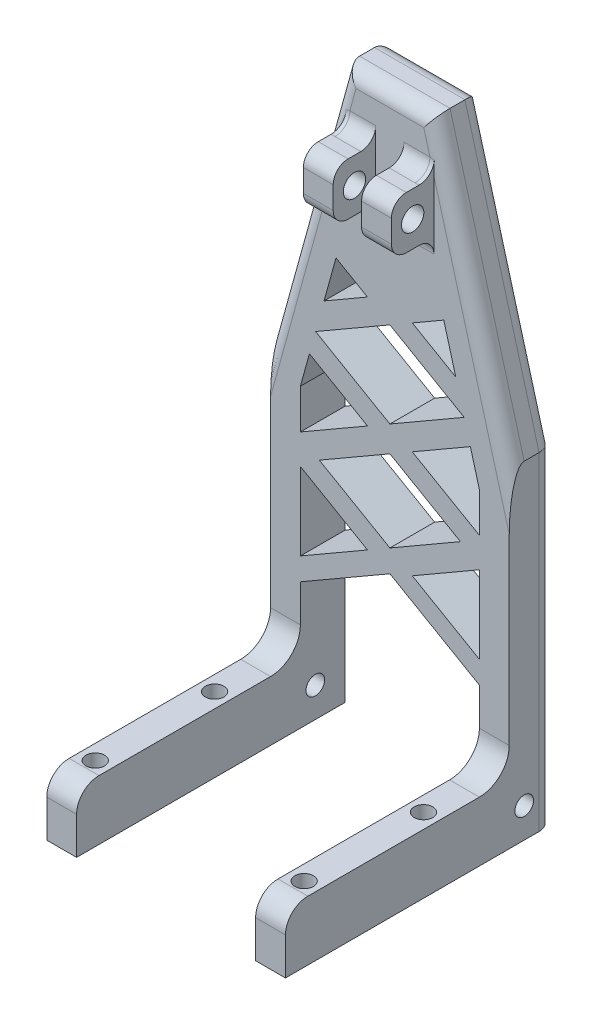
SolidWorks part; units mm, degrees
ref_plane "Front Plane" through (0, 0, 0) normal (0, 0, 1) x (1, 0, 0)
ref_plane "Top Plane" through (0, 0, 0) normal (0, 1, 0) x (1, 0, 0)
ref_plane "Right Plane" through (0, 0, 0) normal (1, 0, 0) x (0, 0, -1)
sketch "Sketch1" plane through (0, 0, 0) normal (0, 1, 0) x (1, 0, 0)
  line L0 (0, 0) -> (0, 15) construction
  line L1 (-12, -15) -> (12, -15) construction
  line L2 (-12, -15) -> (-12, 15) construction
  line L3 (-12, 15) -> (12, 15) construction
  line L4 (12, -15) -> (12, 15) construction
  line L5 (-12, -15) -> (12, 15) construction
  line L6 (-12, 15) -> (12, -15) construction
  line L7 (-12, -15) -> (-16, -15)
  line L8 (-12, -15) -> (-12, 15)
  line L9 (-12, 15) -> (-16, 15)
  line L10 (-16, -15) -> (-16, 15)
  line L11 (12, 15) -> (16, 15)
  line L12 (16, -15) -> (16, 15)
  line L13 (12, -15) -> (16, -15)
  line L14 (12, -15) -> (12, 15)
  line L15 (-14, -15) -> (-14, 15) construction
  circle A0 centre (-14, -10.5) radius 1.25
  circle A1 centre (-14, 5.5) radius 1.25
  circle A2 centre (14, -10.5) radius 1.25
  circle A3 centre (14, 5.5) radius 1.25
  point P0 (0, 0)
  dimension "D5" = 2.5
  dimension "D7" = 2.5
  dimension "D1" = 24
  dimension "D2" = 30
  dimension "D3" = 4
  dimension "D4" = 4.5
  dimension "D6" = 16
extrude "Boss-Extrude1" add sketch "Sketch1" along normal blind 8 contours A1 | A0 | L14 L13 L12 L11 A2 A3 | L8 L7 L10 L9 region at (14, 0, -0.2228) region at (-14, 0, 10.5) region at (-14, 0, -5.5)
ref_plane "Plane1" through (0, 0, 0) normal (-1, 0, 0) x (0, 0, 1)
sketch "Sketch3" plane through (0, 0, 0) normal (-1, 0, 0) x (0, 0, 1)
  line L1 (-15, 0) -> (-21, 0)
  line L2 (-15, 0) -> (-15, 80)
  line L3 (-15, 80) -> (-21, 80)
  line L4 (-21, 0) -> (-21, 80)
  dimension "D1" = 80
  dimension "D2" = 6
extrude "Boss-Extrude2" add sketch "Sketch3" against normal up to surface (16 mm away) and the other way up to surface (16 mm away) up to face at (16, 4, 0) other way up to face at (-16, 4, 0)
sketch "Sketch4" plane through (0, 0, -15) normal (0, 0, 1) x (1, 0, 0)
  line L0 (-12, 8) -> (-12, 0) construction
  line L1 (-12, 39.7004) -> (12, 39.7004)
  line L2 (-12, 39.7004) -> (-12, 0)
  line L3 (-12, 0) -> (12, 0)
  line L4 (12, 39.7004) -> (12, 0)
  line L5 (0, 80) -> (0, 0)
  line L6 (16, 80) -> (-16, 80) construction
  line L7 (-6.0607, 80) -> (6.0607, 80)
  line L8 (-6.0607, 80) -> (-16, 44)
  line L9 (-16, 8) -> (-16, 80) construction
  line L10 (6.0607, 80) -> (16, 44)
  line L11 (16, 80) -> (16, 8) construction
  line L12 (-6.0607, 80) -> (-16, 80)
  line L13 (-16, 80) -> (-16, 44)
  line L14 (6.0607, 80) -> (16, 80)
  line L15 (16, 80) -> (16, 44)
  line L16 (-2.8798, 72.734) -> (2.8798, 72.734)
  line L17 (-2.8798, 72.734) -> (-12, 39.7004)
  line L18 (2.8798, 72.734) -> (12, 39.7004)
  line L19 (-12, 39.7004) -> (12, 39.7004)
  line L20 (-12, 20) -> (-3, 25.1962)
  line L21 (-3, 25.1962) -> (-12, 30.3923)
  line L22 (-12, 32.3923) -> (12, 32.3923) construction
  line L23 (-3, 39.5885) -> (-12, 34.3923)
  line L24 (-12, 44.7846) -> (-3, 39.5885)
  line L25 (12, 20) -> (3, 25.1962)
  line L26 (3, 25.1962) -> (12, 30.3923)
  line L27 (12, 44.7846) -> (3, 39.5885)
  line L28 (3, 39.5885) -> (12, 34.3923)
  line L29 (-12, 17) -> (0, 23.9282)
  line L30 (0, 26.9282) -> (-9.4641, 32.3923)
  line L31 (-9.4641, 32.3923) -> (0, 37.8564)
  line L32 (0, 41.3205) -> (-9.9644, 47.0734)
  line L33 (-9.9644, 47.0734) -> (0, 52.8264)
  line L34 (0, 52.8264) -> (0, 56.2864)
  line L35 (0, 56.2864) -> (-6.4005, 59.9817)
  line L36 (-8.8266, 51.1944) -> (-3.0036, 54.5564)
  line L37 (-3.0036, 54.5564) -> (-7.2254, 56.9939)
  line L38 (0, 56.2864) -> (6.4005, 59.9817)
  line L39 (3.0036, 54.5564) -> (7.2254, 56.9939)
  line L40 (8.8266, 51.1944) -> (3.0036, 54.5564)
  line L41 (9.9644, 47.0734) -> (0, 52.8264)
  line L42 (0, 41.3205) -> (9.9644, 47.0734)
  line L43 (9.4641, 32.3923) -> (0, 37.8564)
  line L44 (0, 26.9282) -> (9.4641, 32.3923)
  line L45 (12, 17) -> (0, 23.9282)
  point P4 (0, 0)
  point P14 (0, 80)
  point P27 (0, 72.734)
  point P55 (0, 0)
  point P56 (-8.2976, 53.1104)
  point P57 (0, 0)
  point P58 (0, 0)
  line M5 (12, 0) -> (12, 8)
  line M7 (16, 8) -> (16, 80)
  line M8 (16, 80) -> (-16, 80)
  line M9 (-16, 80) -> (-16, 8)
  line M11 (-12, 8) -> (-12, 0)
  line M12 (-12, 0) -> (12, 0)
  dimension "D1" = 5
  dimension "D2" = 60
  dimension "D3" = 60
  dimension "D4" = 20
  dimension "D5" = 3
  dimension "D6" = 2
  dimension "D7" = 3
  dimension "D8" = 3
  dimension "D9" = 3
  dimension "D10" = 60
  dimension "D11" = 120
  dimension "D12" = 3
  dimension "D13" = 3
  dimension "D14" = 3.46
extrude "Cut-Extrude2" cut sketch "Sketch4" against normal blind 10 contours L29 L2 L5 M11 M12 | L4 L45 L5 L3 M5 | L20 L21 L2 | L26 L25 L4 | L5 L22 L43 | L31 L22 L5 | L22 L30 L5 | L22 L5 L44 | L27 L28 L4 L19 | L24 L1 L2 L23 | L24 L17 L1 | L18 L27 L19 | L5 L42 L41 | L33 L32 L5 | L36 L37 L17 | L40 L18 L39 | L8 M8 M9 | L10 M8 M7 region at (-8.6611, 41.1622, -15) region at (-8.9406, 37.9295, -15) region at (-12.6869, 68, -15) region at (12.6869, 68, -15) region at (-3.3215, 47.0734, -15) region at (8.6611, 41.1622, -15) region at (8.9406, 37.9295, -15) region at (3.3215, 47.0734, -15) region at (3.1547, 34.2137, -15) region at (-3.1547, 34.2137, -15) region at (-9, 25.1962, -15) region at (-3.1547, 30.5709, -15) region at (-6.3519, 54.2482, -15) region at (3.1547, 30.5709, -15) region at (6.3519, 54.2482, -15) region at (-5.6614, 10.3298, -15) region at (5.6614, 10.3298, -15) region at (9, 25.1962, -15)
sketch "Sketch5" plane through (-16, 0, 0) normal (-1, 0, 0) x (0, 0, 1)
  line L0 (-15, 8) -> (-19, 0)
  line L1 (15, 0) -> (-21, 0) construction
  line L2 (-21, 44) -> (-21, 0) construction
  circle A0 centre (-17, 4) radius 1.25
  point P6 (0, 0)
  point P7 (-18.8866, 0)
  dimension "D1" = 2.5
  dimension "D2" = 2
extrude "Cut-Extrude3" cut sketch "Sketch5" against normal through all contours L0 A0 | L0 A0 region at (-16, 3.7627, -16.5255) region at (-16, 4.2373, -17.4745)
sketch "Sketch6" plane through (0, 0, -15) normal (0, 0, 1) x (1, 0, 0)
  line L0 (0, 52.8264) -> (0, 80)
  line L1 (6.0607, 80) -> (-6.0607, 80) construction
  line L2 (1.9, 66) -> (1.9, 73)
  line L3 (-5.9, 66) -> (-1.9, 66)
  line L4 (-5.9, 66) -> (-5.9, 73)
  line L5 (-5.9, 73) -> (-1.9, 73)
  line L6 (-1.9, 66) -> (-1.9, 73)
  line L7 (5.9, 73) -> (1.9, 73)
  line L8 (5.9, 66) -> (5.9, 73)
  line L9 (5.9, 66) -> (1.9, 66)
  dimension "D1" = 1.9
  dimension "D2" = 7
  dimension "D3" = 4
  dimension "D4" = 7
extrude "Boss-Extrude3" add sketch "Sketch6" along normal blind 5.7 contours L3 L6 L5 L4 | L9 L8 L7 L2 region at (3.9, 69.5, -15) region at (-3.9, 69.5, -15)
sketch "Sketch7" plane through (5.9, 0, 0) normal (1, 0, 0) x (0, 0, -1)
  line L0 (15, 66) -> (9.3, 73)
  line L1 (9.3, 73) -> (15, 73)
  line L2 (15, 73) -> (9.3, 66)
  circle A0 centre (12.15, 69.5) radius 1.5
  dimension "D1" = 3
extrude "Cut-Extrude4" cut sketch "Sketch7" against normal through all contours L0 A0 L2 | L2 A0 L0 | L0 A0 L2 | L2 A0 L0 region at (5.9, 68.576, -12.15) region at (5.9, 69.5, -13.0238) region at (5.9, 69.5, -11.2762) region at (5.9, 70.424, -12.15)
fillet "Fillet4" radius 2 5 edges at (0, 80, -21) (-11.0304, 62, -21) (-16, 22, -21) (16, 22, -21) (11.0304, 62, -21)
fillet "Fillet2" radius 4 2 edges at (-14, 8, -15) (14, 8, -15)
fillet "Fillet3" radius 3 2 edges at (14, 8, 15) (-14, 8, 15)
fillet "Fillet5" radius 2 3 edges at (-11.0304, 62, -15) (11.0304, 62, -15) (0, 80, -15)
fillet "Fillet6" radius 2 4 edges at (3.9, 66, -9.3) (3.9, 73, -9.3) (-3.9, 73, -9.3) (-3.9, 66, -9.3)
fillet "Fillet7" radius 2 4 edges at (3.9, 73, -15) (-3.9, 73, -15) (3.9, 66, -15) (-3.9, 66, -15)
